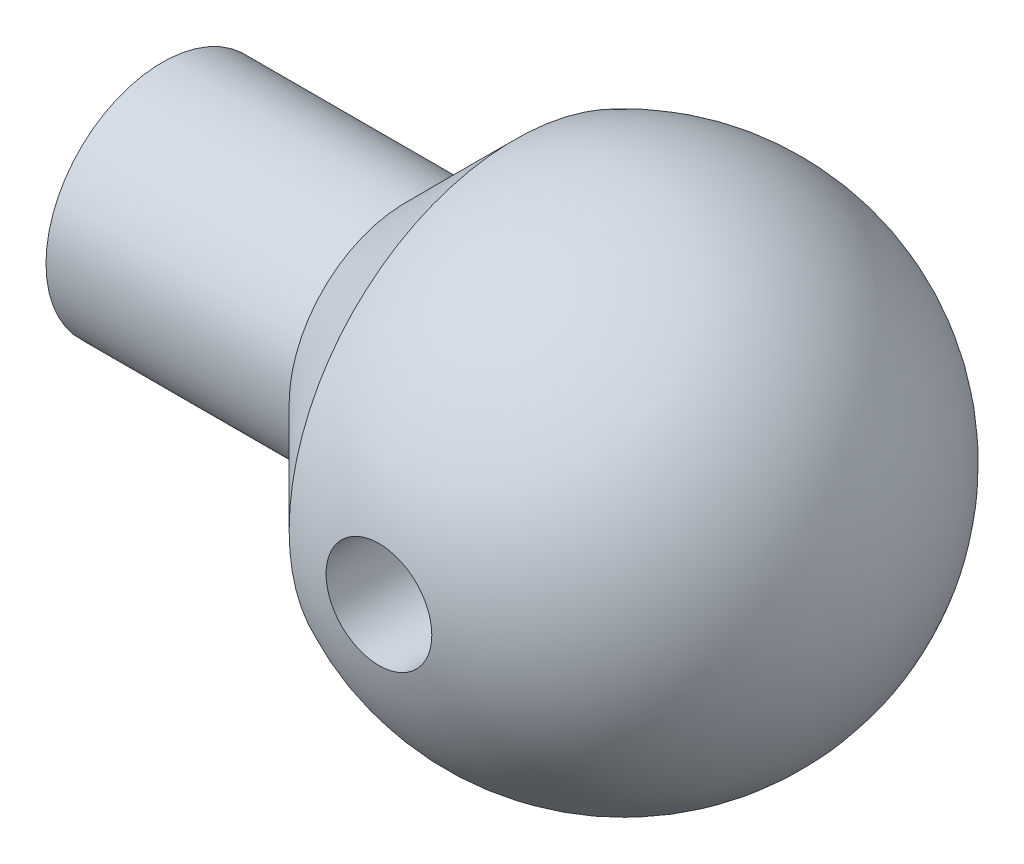
SolidWorks part; units mm, degrees
ref_plane "前视基准面" through (0, 0, 0) normal (0, 0, 1) x (1, 0, 0)
ref_plane "上视基准面" through (0, 0, 0) normal (0, 1, 0) x (1, 0, 0)
ref_plane "右视基准面" through (0, 0, 0) normal (1, 0, 0) x (0, 0, -1)
sketch "草图1" plane through (0, 0, 0) normal (0, 0, 1) x (1, 0, 0)
  line L0 (0, 0) -> (1.9828, -3.3)
  line L1 (1.9828, -3.3) -> (8.8828, -3.3)
  line L2 (0, 0) -> (20.6459, 0) construction
  line L3 (8.8828, -3.3) -> (11.9828, -6.4)
  line L5 (0, 0) -> (22.1941, 0)
  arc A0 (11.9828, -6.4) -> (22.1941, 0) centre (15.0828, 0) ccw
  dimension "D6" = 3.1
  dimension "D5" = 10
  dimension "D4" = 6.4
  dimension "D1" = 59
  dimension "D2" = 3.3
  dimension "D3" = 45
revolve "旋转1" add sketch "草图1" angle 360 about L2
sketch "草图8" plane through (0, 0, 0) normal (0, 0, 1) x (1, 0, 0)
  circle A0 centre (15.0828, 0) radius 1.5
  dimension "2" = 3
extrude "切除-拉伸1" cut sketch "草图8" against normal through all both and the other way through all
scale "缩放比例1" scale about centroid uniform scaling yes scale factor 4.46
